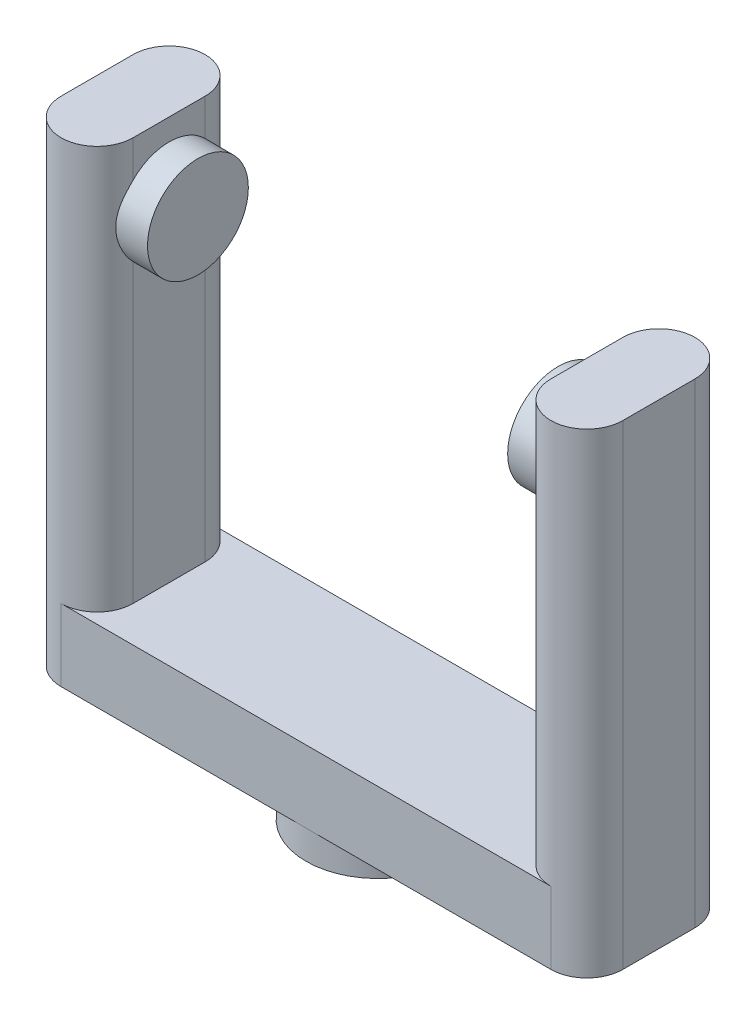
SolidWorks part; units mm, degrees
note: The reader was unsure of these and kept them because the rebuilt part matched: shared geometry of "Esquisse1<6>", "Esquisse1<9>".
ref_plane "Plan de face" through (0, 0, 0) normal (0, 0, 1) x (1, 0, 0)
ref_plane "Plan de dessus" through (0, 0, 0) normal (0, 1, 0) x (1, 0, 0)
ref_plane "Plan de droite" through (0, 0, 0) normal (1, 0, 0) x (0, 0, -1)
sketch "Esquisse1" plane through (0, 0, 0) normal (0, 1, 0) x (1, 0, 0)
  line L1 (0, -5) -> (-19.5, -5)
  line L2 (0, -5) -> (19.5, -5)
  line L3 (0, 5) -> (19.5, 5)
  line L6 (-19.5, -5) -> (-19.5, 5)
  line L7 (-14.5, 0) -> (-19.5, 0)
  line L8 (-19.5, 5) -> (-14.5, 5)
  line L9 (-14.5, 5) -> (-14.5, -5)
  line L10 (-14.5, 5) -> (0, 5)
  line L11 (19.5, 0) -> (14.5, 0)
  line L12 (17, 0) -> (17, -5)
  line L13 (14.5, 2.5) -> (14.5, 5)
  line L14 (14.5, 5) -> (14.5, -5)
  line L15 (-17, 0) -> (-17, -5)
  line L16 (-17, -5) -> (-17, 5)
  line L17 (17, -5) -> (17, 5)
  line L18 (19.5, -5) -> (19.5, 5)
  line L19 (19.5, -2.5) -> (14.5, -2.5)
  line L23 (-14.5, -2.5) -> (-19.5, -2.5)
  line L24 (14.5, 0) -> (-14.5, 0)
  line L26 (-19.5, 2.5) -> (-14.5, 2.5)
  line L27 (14.5, 2.5) -> (19.5, 2.5)
  circle A0 centre (0, 0) radius 3.5
  circle A10 centre (0, 0) radius 5
  arc A23 (19.5, -2.5) -> (17, -5) centre (17, -2.5) cw
  arc A24 (17, -5) -> (14.5, -2.5) centre (17, -2.5) cw
  arc A25 (17, 5) -> (14.5, 2.5) centre (17, 2.5) ccw
  arc A26 (17, 5) -> (19.5, 2.5) centre (17, 2.5) cw
  arc A27 (-17, 5) -> (-19.5, 2.5) centre (-17, 2.5) ccw
  arc A28 (-14.5, 2.5) -> (-17, 5) centre (-17, 2.5) ccw
  arc A29 (-14.5, -2.5) -> (-17, -5) centre (-17, -2.5) cw
  arc A30 (-17, -5) -> (-19.5, -2.5) centre (-17, -2.5) cw
  dimension "D1" = 7
  dimension "D2" = 10
  dimension "D3" = 14.5
  dimension "D6" = 2.5
  dimension "D8" = 2.5
  dimension "D9" = 2.5
  dimension "D11" = 2.5
  dimension "D10" = 2.5
  dimension "D12" = 2.5
  dimension "D4" = 2.5
  dimension "D5" = 14.5
  dimension "D7" = 2.5
extrude "Boss.-Extru.2" add sketch "Esquisse1" against normal blind 5
extrude "Boss.-Extru.3" add sketch "Esquisse1<6>" along normal blind 28
sketch "Esquisse1<6>" plane through (0, 0, 0) normal (0, 1, 0) x (1, 0, 0) same geometry as "Esquisse1"
sketch "Esquisse3" plane through (-14.5, 0, 0) normal (1, 0, 0) x (0, 0, -1)
  line L0 (0, 28) -> (0, 23)
  line L1 (2.5, 28) -> (-2.5, 28) construction
  circle A0 centre (0, 23) radius 3.5
  dimension "D2" = 7
  dimension "D1" = 5
extrude "Boss.-Extru.5" add sketch "Esquisse3" along normal blind 2 and the other way blind 1
extrude "Boss.-Extru.7" add sketch "Esquisse1<9>" against normal blind 7 contours L24 A10 A0 | A10 L24 A0
sketch "Esquisse1<9>" plane through (0, 0, 0) normal (0, 1, 0) x (1, 0, 0) same geometry as "Esquisse1"
sketch "Esquisse4" plane through (14.5, 0, 0) normal (-1, 0, 0) x (0, 0, 1)
  line L0 (0, 28) -> (0, 23)
  line L1 (-2.5, 28) -> (2.5, 28) construction
  circle A0 centre (0, 23) radius 3.5
  dimension "D2" = 7
  dimension "D1" = 5
extrude "Boss.-Extru.8" add sketch "Esquisse4" along normal blind 2 and the other way blind 1
